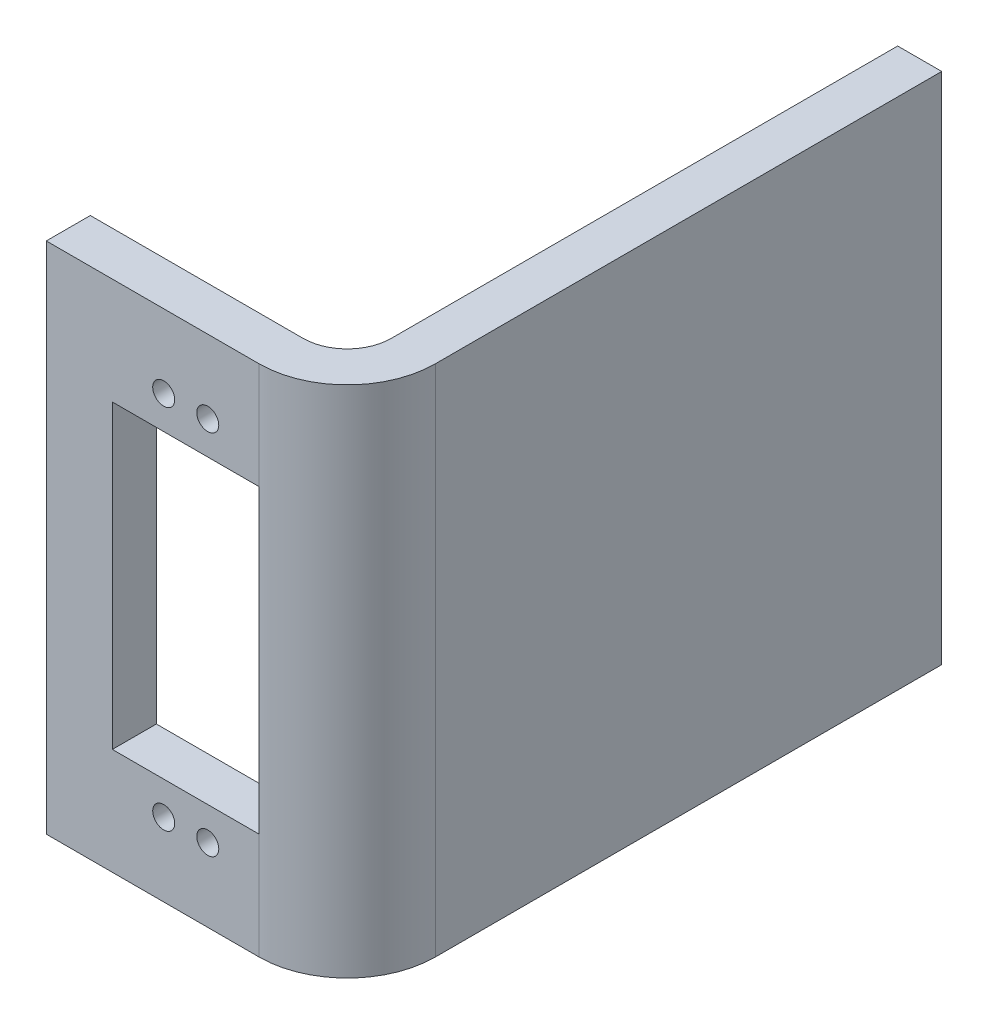
SolidWorks part; units mm, degrees
material "Acrilico TEC"
ref_plane "Front Plane" through (0, 0, 0) normal (0, 0, 1) x (1, 0, 0)
ref_plane "Top Plane" through (0, 0, 0) normal (0, 1, 0) x (1, 0, 0)
ref_plane "Right Plane" through (0, 0, 0) normal (1, 0, 0) x (0, 0, -1)
sketch "Sketch2" plane through (0, 0, 0) normal (0, 1, 0) x (1, 0, 0)
  line L0 (6, 0) -> (6, -69)
  line L1 (0, 0) -> (0, -69)
  line L2 (-6, -75) -> (-35, -75)
  line L3 (-35, -75) -> (-35, -81)
  line L4 (-6, -81) -> (-35, -81)
  line L5 (0, 0) -> (6, 0)
  arc A0 (0, -69) -> (-6, -75) centre (-6, -69) cw
  arc A1 (6, -69) -> (-6, -81) centre (-6, -69) cw
  point P8 (0, -75)
  dimension "D4" = 6
  dimension "D1" = 75
  dimension "D2" = 35
  dimension "D3" = 6
  dimension "D5" = 6
extrude "Boss-Extrude1" add sketch "Sketch2" along normal blind 70 contours A1 L0 L5 L1 A0 L2 L3 L4 region at (5.0921, 0, 34.5)
sketch "Sketch3" plane through (0, 0, 81) normal (0, 0, 1) x (1, 0, 0)
  line L0 (-35, 35) -> (-6, 35) construction
  line L1 (-35, 70) -> (-35, 0) construction
  line L2 (-6, 70) -> (-6, 0) construction
  line L3 (-16, 14.5) -> (-16, 55.5) construction
  line L4 (-13, 10) -> (-19, 10) construction
  line L5 (-16, 10) -> (-16, 60) construction
  line L6 (-16, 60) -> (-19, 60) construction
  line L7 (-26, 55.5) -> (-6, 55.5)
  line L8 (-26, 55.5) -> (-26, 14.5)
  line L9 (-26, 14.5) -> (-6, 14.5)
  line L10 (-6, 55.5) -> (-6, 14.5)
  line L11 (-26, 55.5) -> (-6, 14.5) construction
  line L12 (-26, 14.5) -> (-6, 55.5) construction
  circle A0 centre (-19, 60) radius 1.5
  circle A1 centre (-13, 60) radius 1.5
  circle A2 centre (-13, 10) radius 1.5
  circle A3 centre (-19, 10) radius 1.5
  point P20 (-23, 35)
  dimension "D1" = 3
  dimension "D2" = 25
  dimension "D3" = 6
  dimension "D4" = 20
  dimension "D5" = 41
  dimension "D6" = 10
extrude "Cut-Extrude1" cut sketch "Sketch3" against normal blind 50
